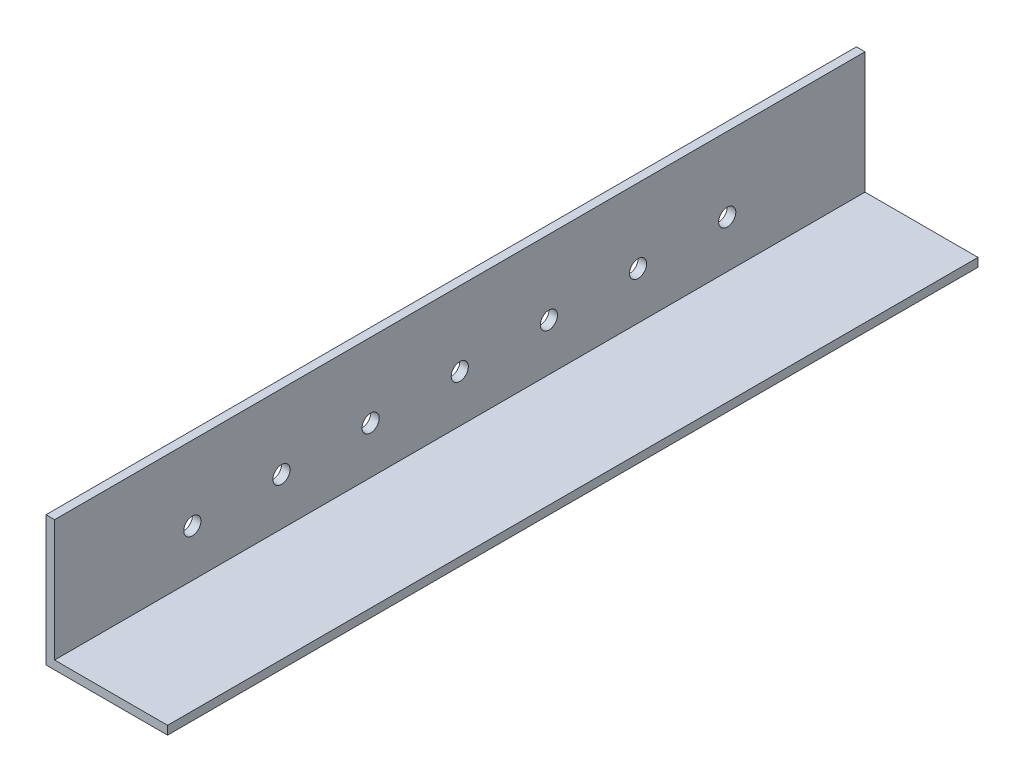
SolidWorks part; units mm, degrees
ref_plane "Alzado" through (0, 0, 0) normal (0, 0, 1) x (1, 0, 0)
ref_plane "Planta" through (0, 0, 0) normal (0, 1, 0) x (1, 0, 0)
ref_plane "Vista lateral" through (0, 0, 0) normal (1, 0, 0) x (0, 0, -1)
sketch "Croquis1" plane through (0, 0, 0) normal (0, 0, 1) x (1, 0, 0)
  line L0 (-19.325, 0) -> (0, 0) construction
  line L1 (22.5, -25.675) -> (-22.5, -25.675)
  line L2 (22.5, -25.675) -> (22.5, -22.5)
  line L3 (22.5, -22.5) -> (-22.5, -22.5)
  line L4 (-22.5, -25.675) -> (-22.5, -22.5)
  line L5 (-22.5, -22.5) -> (-19.325, -22.5)
  line L6 (-22.5, -22.5) -> (-22.5, 22.5)
  line L7 (-22.5, 22.5) -> (-19.325, 22.5)
  line L8 (-19.325, -22.5) -> (-19.325, 22.5)
  line L9 (0, 0) -> (0, -22.5) construction
  dimension "D1" = 3.175
  dimension "D2" = 3.175
  dimension "D3" = 45
  dimension "D4" = 45
extrude "Saliente-Extruir1" add sketch "Croquis1" along normal mid plane 300 contours L3 L8 L7 L6 | L4 L1 L2 L3 region at (0, -24.0875, 0) region at (-20.9125, 0, 0)
sketch "Croquis2" plane through (0, 0, 0) normal (1, 0, 0) x (0, 0, -1)
  line L0 (-185.7724, -5) -> (180.2818, -5) construction
  line L1 (0, 9.483) -> (0, -16.9346) construction
  line L2 (-152.7724, -5) -> (213.2818, -5) construction
  line L3 (-119.7724, -5) -> (246.2818, -5) construction
  line L4 (-86.7724, -5) -> (279.2818, -5) construction
  line L17 (-185.7724, -1.287) -> (180.2818, -1.287) construction
  line L18 (-152.7724, -1.287) -> (213.2818, -1.287) construction
  line L19 (-119.7724, -1.287) -> (246.2818, -1.287) construction
  line L20 (-218.7724, -1.287) -> (147.2818, -1.287) construction
  line L21 (-218.7724, 2.426) -> (147.2818, 2.426) construction
  line L22 (-185.7724, 2.426) -> (180.2818, 2.426) construction
  line L23 (-152.7724, 2.426) -> (213.2818, 2.426) construction
  line L24 (-251.7724, 2.426) -> (114.2818, 2.426) construction
  line L25 (-251.7724, 6.1391) -> (114.2818, 6.1391) construction
  line L26 (-218.7724, 6.1391) -> (147.2818, 6.1391) construction
  line L27 (-185.7724, 6.1391) -> (180.2818, 6.1391) construction
  line L28 (-284.7724, 6.1391) -> (81.2818, 6.1391) construction
  circle A0 centre (0, -5) radius 3.175
  circle A1 centre (33, -5) radius 3.175
  circle A2 centre (66, -5) radius 3.175
  circle A3 centre (99, -5) radius 3.175
  circle A16 centre (-66, 2.426) radius 3.175 [skipped]
  circle A17 centre (-33, 2.426) radius 3.175 [skipped]
  circle A18 centre (-33, -1.287) radius 3.175 [skipped]
  circle A19 centre (-33, 6.1391) radius 3.175 [skipped]
  circle A20 centre (-66, 6.1391) radius 3.175 [skipped]
  circle A21 centre (0, 6.1391) radius 3.175 [skipped]
  circle A22 centre (0, 2.426) radius 3.175 [skipped]
  circle A23 centre (0, -1.287) radius 3.175 [skipped]
  circle A24 centre (33, 2.426) radius 3.175 [skipped]
  circle A25 centre (33, -1.287) radius 3.175 [skipped]
  circle A26 centre (-99, 6.1391) radius 3.175 [skipped]
  circle A27 centre (66, -1.287) radius 3.175 [skipped]
  circle A28 centre (-99, -5) radius 3.175
  circle A29 centre (-66, -5) radius 3.175
  circle A30 centre (-33, -5) radius 3.175
  dimension "D2" = 6.35
  dimension "D1" = 5
  dimension "D5" = 33
  dimension "D3" = 4
  dimension "D4" = 4
extrude "Cortar-Extruir1" cut sketch "Croquis2" against normal blind 50
